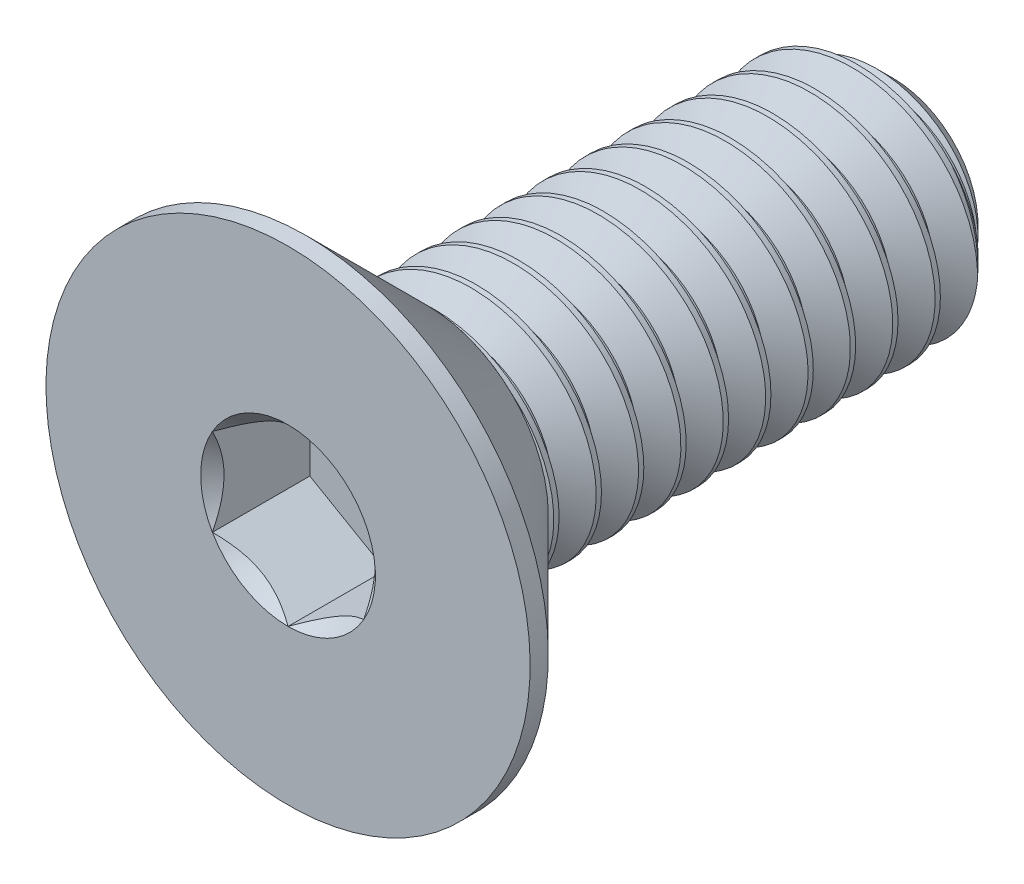
SolidWorks part; units mm, degrees
ref_plane "Front" through (0, 0, 0) normal (0, 0, 1) x (1, 0, 0)
ref_plane "Top" through (0, 0, 0) normal (0, 1, 0) x (1, 0, 0)
ref_plane "Right" through (0, 0, 0) normal (1, 0, 0) x (0, 0, -1)
sketch "Sketch1" plane through (0, 0, 0) normal (1, 0, 0) x (0, 0, -1)
  line L0 (-5, 4) -> (-4.7, 4) construction
  line L1 (-4.7, 4) -> (-2.7, 2) construction
  line L2 (-5, 2) -> (5, 2) construction
  line L3 (5, 2) -> (5, 0) construction
  line L4 (5, 0) -> (-5, 0) construction
  line L5 (-5, 0) -> (-5, 4) construction
  line L6 (-5, 4) -> (-5, -4) construction
  line L7 (5, 2) -> (5, -2) construction
  line L8 (-5, -4) -> (-4.7, -4) construction
  line L9 (-4.7, -4) -> (-2.7, -2) construction
  line L11 (-5, 2) -> (-5, 0) construction
  line L12 (-2.7, 2) -> (-2.7, 0) construction
  line L13 (4.9563, 2.0758) -> (5.3063, 1.4696) construction
  line L14 (5.3063, 1.4696) -> (5.6562, 2.0758) construction
  line L15 (5.6562, 2.0758) -> (4.9563, 2.0758) construction
  line L16 (5.3063, 2.0758) -> (5.3063, 2) construction
  line L17 (5.3063, 2) -> (5.3063, 1.5453) construction
  line L18 (5.3063, 1.5453) -> (5.3063, 1.4696) construction
  line L19 (5.3063, 2.0379) -> (5.6344, 2.0379) construction
  line L20 (5.3063, 2.0379) -> (4.9781, 2.0379) construction
  line L21 (5, 2) -> (5.6125, 2) construction
  line L22 (5.2625, 1.5453) -> (5.35, 1.5453) construction
  line L23 (5, -2) -> (-2.7, -2) construction
  point P10 (3.25, -2)
  point P24 (-2.7, 2)
  point P30 (0, 0)
  dimension "Head Diameter" = 8
  dimension "Head Height" = 2.3
  dimension "Length" = 10
  dimension "Countersink Angle" = 90
  dimension "Thread Pitch" = 0.7
  dimension "D2" = 0.0875
  dimension "Minimum Thread Length" = 7.7
  dimension "Thread Size" = 4
  dimension "D1" = 1.75
sketch "Sketch2" plane through (0, 0, 0) normal (0, 0, 1) x (1, 0, 0)
  line L1 (0, 1.4434) -> (-1.25, 0.7217) construction
  line L2 (-1.25, 0.7217) -> (-1.25, -0.7217) construction
  line L3 (-1.25, -0.7217) -> (0, -1.4434) construction
  line L4 (0, -1.4434) -> (1.25, -0.7217) construction
  line L5 (1.25, -0.7217) -> (1.25, 0.7217) construction
  line L6 (1.25, 0.7217) -> (0, 1.4434) construction
  circle A0 centre (0, 0) radius 1.25 construction
  dimension "Drive Size" = 2.5
sketch "Sketch3" plane through (0, 0, 0) normal (1, 0, 0) x (0, 0, -1)
  line L0 (-5, 2) -> (5, 2)
  line L1 (5, 2) -> (5, 0)
  line L2 (5, 0) -> (-5, 0)
  line L3 (-5, 0) -> (-5, 2)
revolve "Revolve1" add sketch "Sketch3" angle 360 about L4
chamfer "Chamfer1" distance 0.6 angle 45 1 edges at (0, 2, -5)
sketch "Sketch6" plane through (0, 0, 0) normal (1, 0, 0) x (0, 0, -1)
  line L0 (-5, 4) -> (-4.7, 4)
  line L1 (-4.7, 4) -> (-2.7, 2)
  line L2 (-2.7, 2) -> (-2.7, 0)
  line L3 (-2.7, 0) -> (-5, 0)
  line L4 (-5, 0) -> (-5, 4)
revolve "Revolve2" add sketch "Sketch6" angle 360 about L4
sketch "Sketch8" plane through (0, 0, 5) normal (0, 0, 1) x (1, 0, 0)
  line L0 (0, 1.4434) -> (-1.25, 0.7217) construction
  line L1 (1.25, 0.7217) -> (0, 1.4434) construction
  line L2 (1.25, -0.7217) -> (1.25, 0.7217) construction
  line L3 (0, -1.4434) -> (1.25, -0.7217) construction
  line L4 (-1.25, 0.7217) -> (-1.25, -0.7217) construction
  line L5 (-1.25, -0.7217) -> (0, -1.4434) construction
  line L6 (0, 1.4434) -> (-1.25, 0.7217)
  line L7 (1.25, 0.7217) -> (0, 1.4434)
  line L8 (1.25, -0.7217) -> (1.25, 0.7217)
  line L9 (0, -1.4434) -> (1.25, -0.7217)
  line L10 (-1.25, 0.7217) -> (-1.25, -0.7217)
  line L11 (-1.25, -0.7217) -> (0, -1.4434)
extrude "Cut-Extrude1" cut sketch "Sketch8" against normal blind 1.61
sketch "Sketch9" plane through (0, 0, 5) normal (0, 0, 1) x (1, 0, 0)
  circle A0 centre (0, 0) radius 1.4434
extrude "Cut-Extrude2" cut sketch "Sketch9" against normal up to next (1.61 mm away) draft 45
ref_plane "Plane1" through (0, 0, 2.7) normal (0, 0, 1) x (1, 0, 0)
split "Split1" trim tools "Plane1" bodies to split 124 resulting bodies 126 127
sketch "Sketch4" plane through (0, 0, -5) normal (0, 0, -1) x (-1, 0, 0)
  circle A0 centre (0, 0) radius 2 construction
  circle A1 centre (0, 0) radius 2
curve "Helix/Spiral1" pitch 0.7 height 8.4 radius 2 centre (0, 0, -5) axis (0, 0, 1) start towards (0, 1, 0)
sketch "Sketch10" plane through (0, 0, 0) normal (1, 0, 0) x (0, 0, -1)
  line L0 (4.9781, 2.0379) -> (5.6344, 2.0379)
  line L1 (5.6344, 2.0379) -> (5.35, 1.5453)
  line L2 (5.35, 1.5453) -> (5.2625, 1.5453)
  line L3 (5.2625, 1.5453) -> (4.9781, 2.0379)
sweep "Cut-Sweep1" cut profiles "Sketch10" path "Helix/Spiral1"
equation "\"D2@Sketch1\" = \"Thread Pitch@Sketch1\" / 8"
equation "\"D4@Helix/Spiral1\"=\"Thread Pitch@Sketch1\""
equation "\"D3@Helix/Spiral1\"=\"Minimum Thread Length@Sketch1\"+\"Thread Pitch@Sketch1\""
equation "\"D1@Chamfer1\"=\"Thread Size@Sketch1\"*.15"
equation "\"D1@Cut-Extrude1\"=\"Head Height@Sketch1\"*.7"
equation "\"D1@Sketch1\"=\"Thread Pitch@Sketch1\"*2.5"
